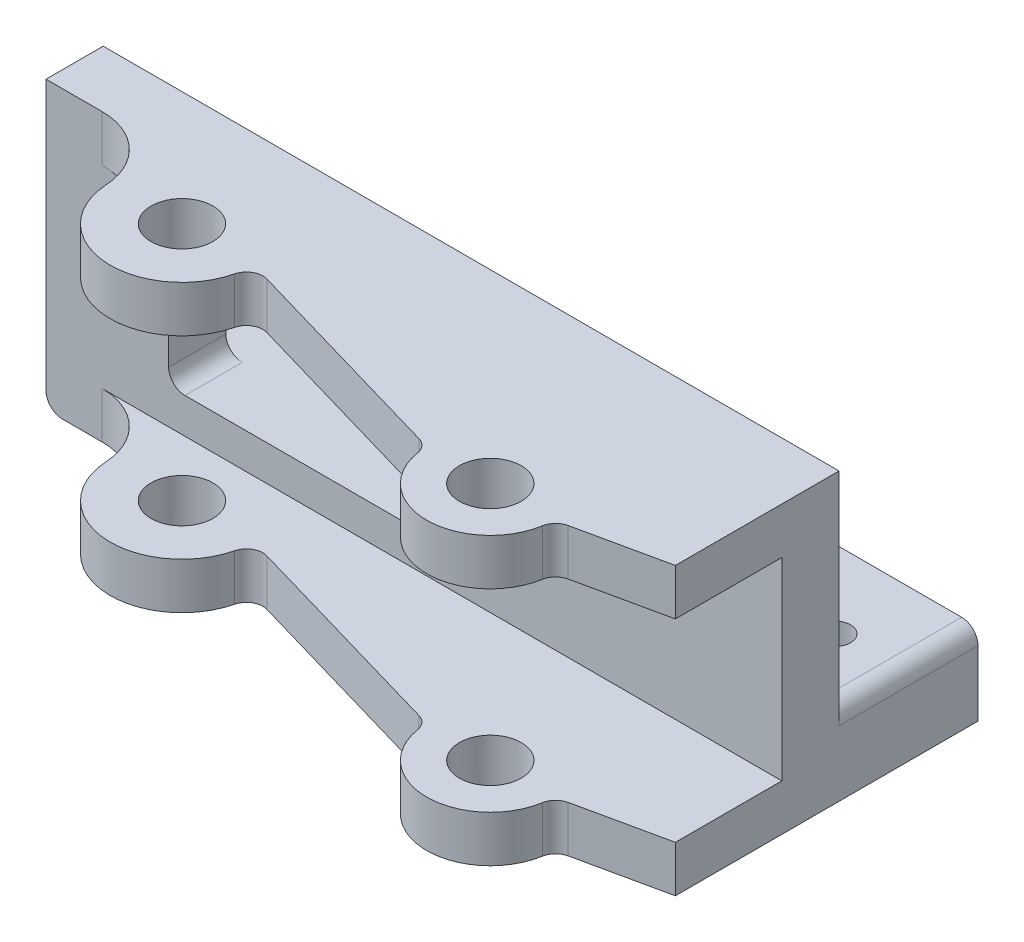
SolidWorks part; units mm, degrees
ref_plane "Front Plane" through (0, 0, 0) normal (0, 0, 1) x (1, 0, 0)
ref_plane "Top Plane" through (0, 0, 0) normal (0, 1, 0) x (1, 0, 0)
ref_plane "Right Plane" through (0, 0, 0) normal (1, 0, 0) x (0, 0, -1)
sketch "Sketch1" plane through (0, 0, 0) normal (0, 0, 1) x (1, 0, 0)
  line L1 (57.15, -22.225) -> (-57.15, -22.225)
  line L2 (57.15, -22.225) -> (57.15, 22.225)
  line L3 (57.15, 22.225) -> (-57.15, 22.225)
  line L4 (-57.15, -22.225) -> (-57.15, 22.225)
  line L5 (57.15, -22.225) -> (-57.15, 22.225) construction
  line L6 (57.15, 22.225) -> (-57.15, -22.225) construction
  point P0 (0, 0)
  dimension "D1" = 44.45
  dimension "D2" = 114.3
extrude "Boss-Extrude1" add sketch "Sketch1" along normal blind 62.23
sketch "Sketch2" plane through (0, 0, 62.23) normal (0, 0, 1) x (1, 0, 0)
  line L0 (-57.15, 22.225) -> (-57.15, -22.225) construction
  line L1 (57.15, -15.025) -> (-57.15, -15.025)
  line L2 (57.15, -15.025) -> (57.15, 15.025)
  line L3 (57.15, 15.025) -> (-57.15, 15.025)
  line L4 (-57.15, -15.025) -> (-57.15, 15.025)
  line L5 (57.15, -15.025) -> (-57.15, 15.025) construction
  line L6 (57.15, 15.025) -> (-57.15, -15.025) construction
  line L7 (57.15, 22.225) -> (-57.15, 22.225) construction
  point P0 (0, 0)
  dimension "D1" = 7.2
extrude "Cut-Extrude2" cut sketch "Sketch2" against normal blind 31.75
sketch "Sketch3" plane through (0, 0, 0) normal (0, 0, -1) x (-1, 0, 0)
  line L0 (-57.15, -22.225) -> (-57.15, 22.225) construction
  line L1 (57.15, 22.225) -> (-57.15, 22.225)
  line L2 (57.15, 22.225) -> (57.15, -9.525)
  line L3 (57.15, -9.525) -> (-57.15, -9.525)
  line L4 (-57.15, 22.225) -> (-57.15, -9.525)
  line L5 (57.15, -22.225) -> (-57.15, -22.225) construction
  dimension "D1" = 12.7
extrude "Cut-Extrude3" cut sketch "Sketch3" against normal blind 21.59
sketch "Sketch5" plane through (0, -22.225, 0) normal (0, -1, 0) x (1, 0, 0)
  line L0 (-3.81, 12.06) -> (46.99, 12.06) construction
  line L1 (57.15, 21.59) -> (-57.15, 21.59) construction
  line L2 (57.15, 62.23) -> (57.15, 0) construction
  circle A0 centre (-3.81, 12.06) radius 2.415
  circle A1 centre (46.99, 12.06) radius 2.415
  dimension "D3" = 4.83
  dimension "D4" = 10.16
  dimension "D1" = 9.53
  dimension "D2" = 50.8
extrude "Cut-Extrude4" cut sketch "Sketch5" against normal blind 25.4
sketch "Sketch6" plane through (0, 0, 21.59) normal (0, 0, -1) x (-1, 0, 0)
  line L0 (-49.405, -9.525) -> (6.225, -9.525) construction
  line L1 (-49.405, -9.525) -> (-49.405, -22.225) construction
  line L2 (6.225, -22.225) -> (6.225, -9.525) construction
  line L3 (-57.15, -9.525) -> (57.15, -9.525) construction
  line L6 (-29.083, 1.651) -> (-29.083, 6.477) construction
  line L7 (-22.4401, 6.477) -> (-22.4401, 1.651) construction
  line L8 (-29.083, 6.477) -> (-14.097, 6.477) construction
  line L9 (-19.177, 1.651) -> (-29.083, 1.651) construction
  circle A1 centre (-26.8605, 4.064) radius 2.2225
  dimension "D3" = 4.445
extrude "Cut-Extrude5" cut sketch "Sketch6" against normal blind 5.08
sketch "Sketch7" plane through (0, -22.225, 0) normal (0, -1, 0) x (1, 0, 0)
  line L0 (57.15, 62.23) -> (57.15, 0) construction
  line L1 (-57.15, 0) -> (57.15, 0) construction
  circle A0 centre (31.75, 50.36) radius 4.8
  circle A1 centre (-27.14, 39.37) radius 4.8
  dimension "D1" = 9.6
  dimension "D2" = 25.4
  dimension "D3" = 39.37
  dimension "D4" = 9.6
  dimension "D5" = 58.89
  dimension "D6" = 10.99
extrude "Cut-Extrude6" cut sketch "Sketch7" against normal up to surface (44.45 mm away) up to face at (0, 22.225, 41.91)
sketch "Sketch9" plane through (0, 0, 30.48) normal (0, 0, 1) x (1, 0, 0)
  line L5 (57.15, 15.025) -> (-57.15, 15.025) construction
  line L6 (-38.1, 15.025) -> (6.35, 15.025)
  line L7 (-38.1, 15.025) -> (-38.1, -15.025)
  line L8 (-38.1, -15.025) -> (6.35, -15.025)
  line L9 (6.35, 15.025) -> (6.35, -15.025)
  line L10 (-57.15, -15.025) -> (57.15, -15.025) construction
  line L11 (-57.15, 15.025) -> (-57.15, -15.025) construction
  line L12 (57.15, -15.025) -> (57.15, 15.025) construction
  dimension "D1" = 50.8
  dimension "25in" = 19.05
extrude "Cut-Extrude7" cut sketch "Sketch9" against normal through all both and the other way through all
sketch "Sketch16" plane through (0, -22.225, 0) normal (0, -1, 0) x (1, 0, 0)
  line L1 (-38.1, 30.48) -> (-57.15, 30.48) construction
  line L8 (-57.15, 62.23) -> (57.15, 62.23)
  line L9 (57.15, 62.23) -> (57.15, 47.0103)
  line L10 (57.15, 62.23) -> (57.15, 0) construction
  line L11 (-15.99, 39.37) -> (21.87, 50.36)
  line L12 (41.63, 50.36) -> (57.15, 47.0103)
  line L13 (-48.4121, 30.48) -> (-57.15, 30.48)
  line L15 (-57.15, 30.48) -> (-57.15, 62.23)
  arc A2 (41.63, 50.36) -> (21.87, 50.36) centre (31.75, 50.36) ccw
  arc A3 (-15.99, 39.37) -> (-38.2702, 40.0345) centre (-27.14, 39.37) ccw
  circle A4 centre (-27.14, 39.37) radius 4.8 construction
  circle A5 centre (31.75, 50.36) radius 4.8 construction
  arc A6 (-48.4121, 30.48) -> (-38.2702, 40.0345) centre (-48.4121, 40.64) ccw
  dimension "D1" = 6.35
  dimension "D2" = 5.08
  dimension "D3" = 10.16
extrude "Cut-Extrude8" cut sketch "Sketch16" against normal through all
fillet "Fillet1" radius 2.54 6 edges at (21.87, 18.625, 50.36) (41.63, -18.625, 50.36) (41.63, 18.625, 50.36) (-15.99, 18.625, 39.37) (-15.99, -18.625, 39.37) (21.87, -18.625, 50.36)
sketch "Sketch14" plane through (6.35, 0, 0) normal (-1, 0, 0) x (0, 0, 1)
  line L0 (0, -15.025) -> (30.48, -15.025) construction
  line L1 (21.59, -9.525) -> (0, -9.525)
  line L2 (21.59, -9.525) -> (21.59, -15.025)
  line L3 (21.59, -15.025) -> (0, -15.025)
  line L4 (0, -9.525) -> (0, -15.025)
extrude "Boss-Extrude2" add sketch "Sketch14" along normal up to next
sketch "Sketch17" plane through (0, 0, 21.59) normal (0, 0, 1) x (1, 0, 0)
  line L1 (6.35, -15.025) -> (-38.1, -15.025)
  line L2 (6.35, -15.025) -> (6.35, -9.525)
  line L3 (6.35, -9.525) -> (-38.1, -9.525)
  line L4 (-38.1, -15.025) -> (-38.1, -9.525)
extrude "Boss-Extrude3" add sketch "Sketch17" along normal up to surface (8.89 mm away) up to face at (31.75, 0, 30.48)
sketch "Sketch18" plane through (-57.15, 0, 0) normal (-1, 0, 0) x (0, 0, 1)
  line L0 (30.48, 22.225) -> (30.48, -22.225) construction
  line L1 (21.59, 22.225) -> (30.48, 22.225)
  line L2 (21.59, 22.225) -> (21.59, -22.225)
  line L3 (21.59, -22.225) -> (30.48, -22.225)
  line L4 (30.48, 22.225) -> (30.48, -22.225)
  line L5 (21.59, 22.225) -> (30.48, -22.225) construction
  line L6 (21.59, -22.225) -> (30.48, 22.225) construction
  line L7 (30.48, -22.225) -> (0, -22.225) construction
  line L8 (21.59, -9.525) -> (21.59, 22.225) construction
  line L9 (30.48, 22.225) -> (21.59, 22.225) construction
  point P0 (26.035, 0)
sketch "Sketch20" plane through (0, 0, 21.59) normal (0, 0, -1) x (-1, 0, 0)
  line L0 (38.1, 15.025) -> (38.1, -9.525) construction
  line L1 (38.1, 38.1) -> (88.9, 38.1)
  line L2 (38.1, 38.1) -> (38.1, -38.1)
  line L3 (38.1, -38.1) -> (88.9, -38.1)
  line L4 (88.9, 38.1) -> (88.9, -38.1)
  line L5 (38.1, 38.1) -> (88.9, -38.1) construction
  line L6 (38.1, -38.1) -> (88.9, 38.1) construction
  point P0 (63.5, 0)
  point P9 (88.9, 0)
  dimension "D1" = 76.2
  dimension "D2" = 50.8
sketch "Sketch21" plane through (0, 0, 30.48) normal (0, 0, 1) x (1, 0, 0)
  line L0 (-54.61, -20.32) -> (-54.61, -19.685)
  line L13 (-54.61, 19.685) -> (-54.61, -19.685)
  line L14 (-54.61, 19.685) -> (-54.61, -19.685)
  line L16 (-50.9521, -12.485) -> (-40.64, -12.485)
  line L17 (-40.64, -12.485) -> (-40.64, -12.065)
  line L34 (-54.61, -19.685) -> (-50.9521, -19.685)
  line L35 (-50.9521, -19.685) -> (-50.9521, -12.485)
  line L36 (-50.9521, -12.485) -> (54.61, -12.485)
  line L37 (54.61, -12.485) -> (54.61, 12.485)
  line L38 (54.61, 12.485) -> (8.89, 12.485)
  line L39 (8.89, 12.485) -> (8.89, -12.065)
  line L40 (8.89, -12.065) -> (-40.64, -12.065)
  line L41 (-40.64, -12.065) -> (-40.64, 12.485)
  line L42 (-40.64, 12.485) -> (-50.9521, 12.485)
  line L43 (-50.9521, 12.485) -> (-50.9521, 19.685)
  line L44 (-50.9521, 19.685) -> (-54.61, 19.685)
  line L50 (-54.61, -19.685) -> (-50.9521, -19.685)
  line L51 (-50.9521, -19.685) -> (-50.9521, -12.485)
  line L57 (-40.64, -12.065) -> (-40.64, 12.485)
  line L58 (-40.64, 12.485) -> (-50.9521, 12.485)
  line L59 (-50.9521, 12.485) -> (-50.9521, 19.685)
  line L60 (-50.9521, 19.685) -> (-54.61, 19.685)
  dimension "D1" = 2.54
fillet "Fillet6" radius 2.54 7 edges at (6.35, -9.525, 26.035) (6.35, 15.025, 26.035) (-38.1, 15.025, 26.035) (-38.1, -9.525, 26.035) (57.15, -9.525, 10.795) (-57.15, -9.525, 10.795) (-57.15, -22.225, 15.24)
